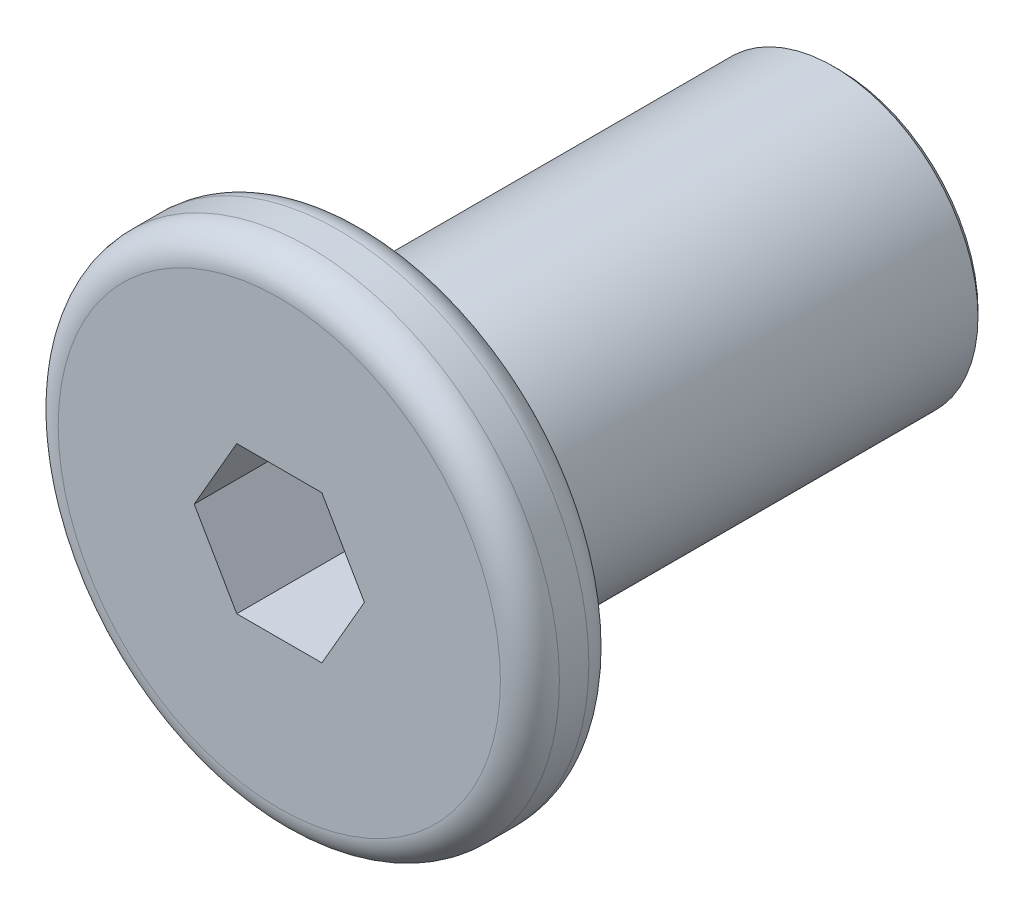
SolidWorks part; units mm, degrees
material "Простая углеродистая сталь"
ref_plane "Спереди" through (0, 0, 0) normal (0, 0, 1) x (1, 0, 0)
ref_plane "Сверху" through (0, 0, 0) normal (0, 1, 0) x (1, 0, 0)
ref_plane "Справа" through (0, 0, 0) normal (1, 0, 0) x (0, 0, -1)
sketch "Эскиз1" plane through (0, 0, 0) normal (0, 0, 1) x (1, 0, 0)
  circle A0 centre (0, 0) radius 4.25
  dimension "D1" = 8.5
extrude "Бобышка-Вытянуть1" add sketch "Эскиз1" along normal blind 1.5
sketch "Эскиз2" plane through (0, 0, 0) normal (0, 0, -1) x (-1, 0, 0)
  circle A0 centre (0, 0) radius 2.45
  dimension "D1" = 4.9
extrude "Бобышка-Вытянуть2" add sketch "Эскиз2" along normal blind 8
fillet "Скругление1" radius 0.5 2 edges at (4.25, 0, 1.5) (4.25, 0, 0)
sketch "Эскиз3" plane through (0, 0, 1.5) normal (0, 0, 1) x (1, 0, 0)
  line L1 (1.4434, 0) -> (0.7217, 1.25)
  line L2 (0.7217, 1.25) -> (-0.7217, 1.25)
  line L3 (-0.7217, 1.25) -> (-1.4434, 0)
  line L4 (-1.4434, 0) -> (-0.7217, -1.25)
  line L5 (-0.7217, -1.25) -> (0.7217, -1.25)
  line L6 (0.7217, -1.25) -> (1.4434, 0)
  circle A0 centre (0, 0) radius 1.25 construction
  dimension "D1" = 2.5
extrude "Вырез-Вытянуть1" cut sketch "Эскиз3" against normal blind 2
sketch "Skizze2" plane through (0, 0, -8) normal (0, 0, -1) x (-1, 0, 0)
  circle A0 centre (0, 0) radius 1.65
  dimension "D1" = 3.3
extrude "Schnitt-Linear austragen1" cut sketch "Skizze2" against normal offset from surface (7 mm away) 1 up to face at (3.75, 0, 0)
thread "Gewinde2" pitch 0.7 method cut profile "Gewindeprofil2" start angle 0, offset 1, length 0, pitch 0.7, diameter 3.3
ref_plane "Ebene2" through (1.65, 0, -9) normal (0, -1, 0) x (1, 0, 0)
sketch "Gewindeprofil2" plane through (1.65, 0, -9) normal (0, -1, 0) x (1, 0, 0)
  line L0 (0, 0) -> (0, 0.7) construction
  line L1 (0, 0) -> (0.3789, 0.2187)
  line L2 (0.3789, 0.2187) -> (0.3789, 0.3062)
  line L3 (0.3789, 0.3062) -> (0, 0.525)
  line L4 (0.3789, 0.2625) -> (0, 0.2625) construction
  line L11 (0, 0) -> (0, 0.525)
  point P2 (0, 0)
  dimension "Pitch" = 0.7
  dimension "Profile_Angle" = 60
  dimension "Profile_Land" = 0.0875
  dimension "Profile_Height" = 0.3789
sketch "Skizze7" plane through (0, 0, 0) normal (0, 1, 0) x (1, 0, 0)
  line L0 (0, 8) -> (2.1, 8)
  line L1 (2.45, 8) -> (-2.45, 8) construction
  line L2 (0, 8) -> (0, 24.3824) construction
  line L4 (1.5236, 8) -> (-1.4842, 8) construction
  line L5 (2.1, 8) -> (1.6, 7.5)
  line L6 (1.6, 7.5) -> (0, 7.5)
  line L7 (0, 7.5) -> (0, 8)
  dimension "D1" = 2.1
  dimension "D2" = 45
  dimension "D3" = 0.5
revolve "Schnitt-Rotation2" cut sketch "Skizze7" angle 360 about L7
chamfer "Fase2" distance 0.1 angle 45 1 edges at (-2.45, 0, -8)
